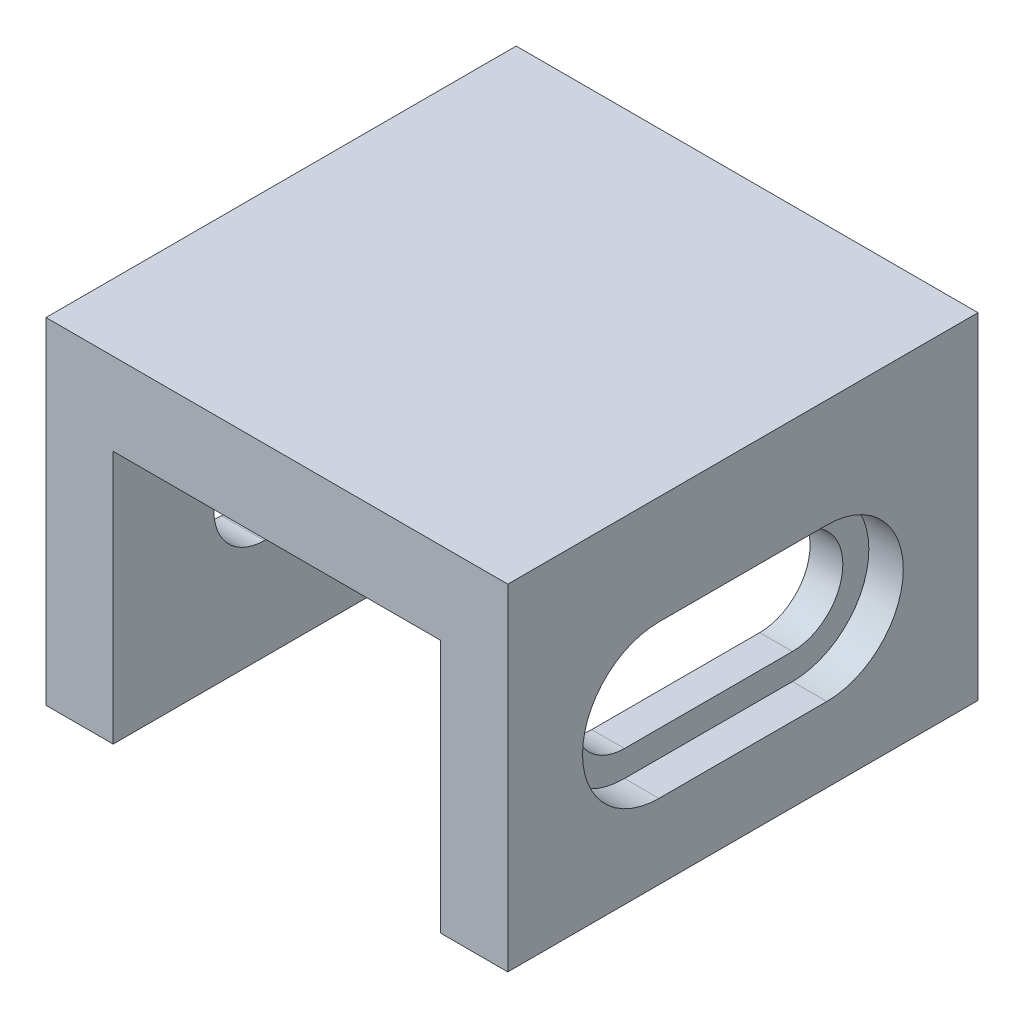
SolidWorks part; units mm, degrees
ref_plane "Front Plane" through (0, 0, 0) normal (0, 0, 1) x (1, 0, 0)
ref_plane "Top Plane" through (0, 0, 0) normal (0, 1, 0) x (1, 0, 0)
ref_plane "Right Plane" through (0, 0, 0) normal (1, 0, 0) x (0, 0, -1)
sketch "Sketch1" plane through (0, 0, 0) normal (0, 1, 0) x (1, 0, 0)
  line L1 (0, 0) -> (27.5, 0)
  line L2 (0, 0) -> (0, 28)
  line L3 (0, 28) -> (27.5, 28)
  line L4 (27.5, 0) -> (27.5, 28)
  dimension "D1" = 27.5
  dimension "D2" = 28
extrude "Boss-Extrude1" add sketch "Sketch1" along normal blind 20
sketch "Sketch2" plane through (0, 0, 0) normal (-1, 0, 0) x (0, 0, 1)
  line L0 (0, 20) -> (0, 0) construction
  line L1 (-28, 0) -> (0, 0) construction
  line L2 (-28, 20) -> (-28, 0) construction
  line L4 (-19, 12) -> (-9, 12)
  line L6 (-19, 6) -> (-9, 6)
  arc A0 (-9, 6) -> (-9, 12) centre (-9, 9) ccw
  arc A1 (-19, 12) -> (-19, 6) centre (-19, 9) ccw
  dimension "D1" = 6
  dimension "D4" = 9
  dimension "D6" = 6
  dimension "D2" = 9
  dimension "D5" = 9
extrude "Cut-Extrude1" cut sketch "Sketch2" against normal blind 27.5
sketch "Sketch3" plane through (0, 0, 0) normal (-1, 0, 0) x (0, 0, 1)
  line L1 (-19, 13.55) -> (-9, 13.55)
  line L3 (-19, 4.45) -> (-9, 4.45)
  arc A0 (-9, 4.45) -> (-9, 13.55) centre (-9, 9) ccw
  arc A1 (-19, 13.55) -> (-19, 4.45) centre (-19, 9) ccw
  dimension "D1" = 9.1
  dimension "D2" = 9.1
extrude "Cut-Extrude2" cut sketch "Sketch3" against normal blind 1.45
sketch "Sketch4" plane through (27.5, 0, 0) normal (1, 0, 0) x (0, 0, -1)
  line L1 (9, 13.55) -> (19, 13.55)
  line L3 (9, 4.45) -> (19, 4.45)
  arc A0 (9, 13.55) -> (9, 4.45) centre (9, 9) ccw
  arc A1 (19, 4.45) -> (19, 13.55) centre (19, 9) ccw
  dimension "D1" = 9.1
  dimension "D2" = 9.1
extrude "Cut-Extrude3" cut sketch "Sketch4" against normal blind 2.05
sketch "Sketch5" plane through (0, 0, 0) normal (0, 1, 0) x (1, 0, 0)
  line L0 (27.5, 28) -> (0, 28) construction
  line L1 (4, 28) -> (23.5, 28)
  line L2 (4, 28) -> (4, 0)
  line L3 (4, 0) -> (23.5, 0)
  line L4 (23.5, 28) -> (23.5, 0)
  line L5 (0, 0) -> (27.5, 0) construction
  line L6 (0, 28) -> (0, 0) construction
  line L7 (27.5, 0) -> (27.5, 28) construction
  dimension "D1" = 4
  dimension "D2" = 4
extrude "Cut-Extrude4" cut sketch "Sketch5" along normal blind 15.1
